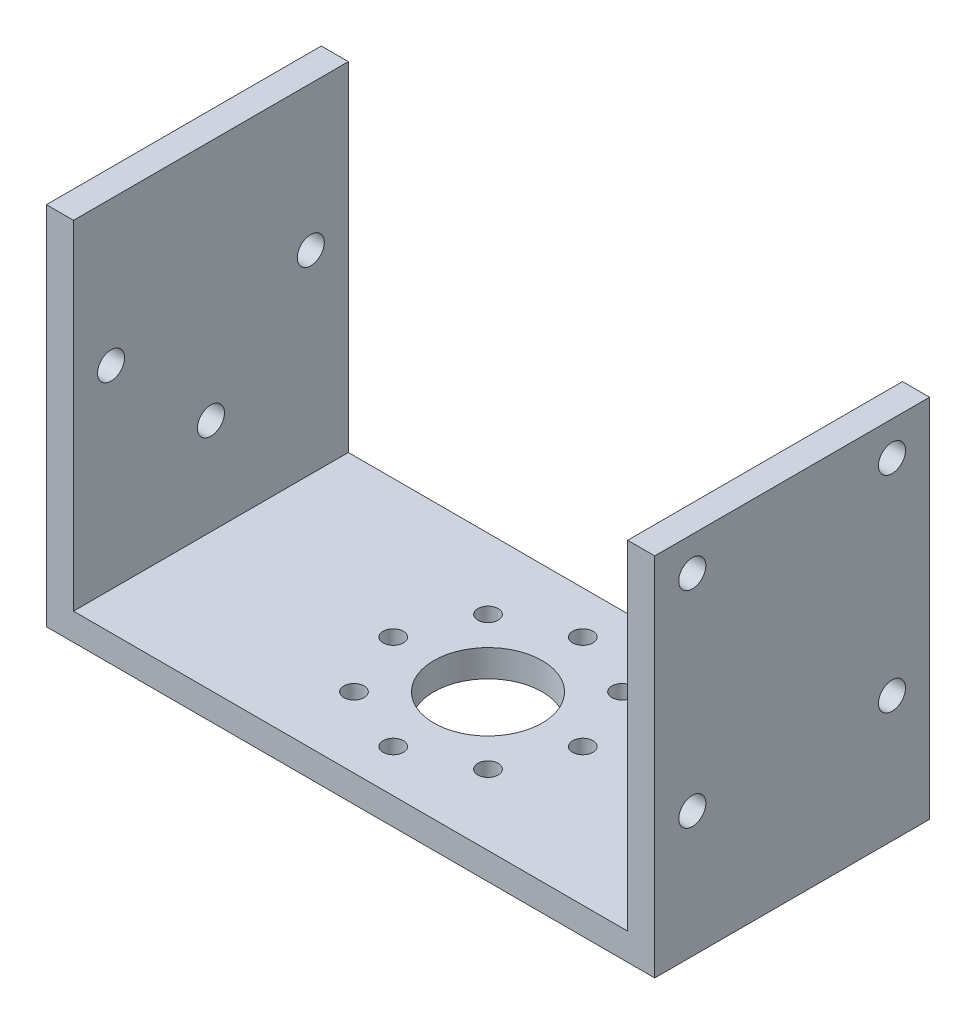
SolidWorks part; units mm, degrees
ref_plane "Front Plane" through (0, 0, 0) normal (0, 0, 1) x (1, 0, 0)
ref_plane "Top Plane" through (0, 0, 0) normal (0, 1, 0) x (1, 0, 0)
ref_plane "Right Plane" through (0, 0, 0) normal (1, 0, 0) x (0, 0, -1)
sketch "Sketch1" plane through (0, 0, 0) normal (0, 1, 0) x (1, 0, 0)
  line L1 (0, 0) -> (44.93, 0)
  line L2 (0, 0) -> (0, 20.3)
  line L3 (0, 20.3) -> (44.93, 20.3)
  line L4 (44.93, 0) -> (44.93, 20.3)
  dimension "D1" = 44.93
  dimension "D2" = 20.3
extrude "YawMount" add sketch "Sketch1" along normal blind 2
sketch "Sketch2" plane through (0, 2, 0) normal (0, 1, 0) x (1, 0, 0)
  line L0 (0, 0) -> (44.93, 0) construction
  line L1 (0, 20.3) -> (2, 20.3)
  line L2 (0, 20.3) -> (0, 0)
  line L3 (0, 0) -> (2, 0)
  line L4 (2, 20.3) -> (2, 0)
  line L6 (44.93, 20.3) -> (42.93, 20.3)
  line L7 (44.93, 20.3) -> (44.93, 0)
  line L8 (44.93, 0) -> (42.93, 0)
  line L9 (42.93, 20.3) -> (42.93, 0)
  dimension "D1" = 2
  dimension "D2" = 2
extrude "BodyConnectors" add sketch "Sketch2" along normal blind 25
sketch "Sketch3" plane through (0, 0, 0) normal (0, -1, 0) x (1, 0, 0)
  line L0 (0, -20.3) -> (0, 0) construction
  line L1 (44.93, -20.3) -> (0, -20.3) construction
  circle A0 centre (22.465, -10.15) radius 4
  point P4 (0, -10.15)
  point P7 (22.465, -20.3)
  dimension "D1" = 8
extrude "Axle-Counterbore" cut sketch "Sketch3" against normal up to surface (2 mm away) up to face at (22.465, 2, -10.15)
sketch "Sketch5" plane through (0, 0, 0) normal (0, -1, 0) x (1, 0, 0)
  line L0 (0, -20.3) -> (0, 0) construction
  line L1 (44.93, -20.3) -> (0, -20.3) construction
  circle A0 centre (15.465, -10.15) radius 0.75
  circle A4 centre (17.5153, -5.2003) radius 0.75
  circle A5 centre (22.465, -3.15) radius 0.75
  circle A6 centre (27.4147, -5.2003) radius 0.75
  circle A7 centre (29.465, -10.15) radius 0.75
  circle A8 centre (27.4147, -15.0997) radius 0.75
  circle A9 centre (22.465, -17.15) radius 0.75
  circle A10 centre (17.5153, -15.0997) radius 0.75
  point P6 (0, -10.15)
  point P24 (22.465, -10.15)
  point P25 (22.465, -20.3)
  dimension "D1" = 1.5
  dimension "D2" = 7
  dimension "D3" = 8
extrude "azel-mountscrews" cut sketch "Sketch5" against normal up to surface (2 mm away) up to face at (22.465, 2, -14.15)
sketch "Sketch6" plane through (2, 0, 0) normal (1, 0, 0) x (0, 0, -1)
  line L0 (0, 27) -> (20.3, 27) construction
  line L3 (0, 2) -> (20.3, 2) construction
  circle A1 centre (10.15, 9.12) radius 1
  circle A2 centre (17.525, 16.33) radius 1
  circle A3 centre (2.775, 16.33) radius 1
  point P5 (10.15, 27)
  dimension "D2" = 2
  dimension "D3" = 14.75
  dimension "D4" = 7.21
  dimension "D5" = 7.375
  dimension "D1" = 7.12
extrude "GearSide-Screws" cut sketch "Sketch6" against normal up to surface (2 mm away) up to face at (0, 13.5, -10.15)
sketch "Sketch7" plane through (42.93, 0, 0) normal (-1, 0, 0) x (0, 0, 1)
  line L0 (-20.3, 2) -> (0, 2) construction
  circle A0 centre (-2.775, 9.3) radius 1
  circle A1 centre (-17.525, 9.3) radius 1
  circle A2 centre (-17.525, 24.5) radius 1
  circle A3 centre (-2.775, 24.5) radius 1
  point P14 (-10.15, 2)
  dimension "D2" = 2
  dimension "D3" = 14.75
  dimension "D1" = 7.3
  dimension "D4" = 7.375
  dimension "D5" = 15.2
extrude "SmoothSide-Screws" cut sketch "Sketch7" against normal up to surface (2 mm away) up to face at (44.93, 13.5, -10.15)
equation "\"srv_w\"= 40.43mm'width of Sain Smart SR319"
equation "\"D1@Sketch1\"=\"srv_w\" + \"mnt_thick\"*2.25"
equation "\"srv_h\"= 40.61mm'height of Sain Smart SR319"
equation "\"srv_d\"= 20.3mm'depth of Sain Smart SR319"
equation "\"D2@Sketch1\"=\"srv_d\""
equation "\"mnt_thick\"= 2mm'thickness of bracket"
equation "\"D1@YawMount\" = \"mnt_thick\""
equation "\"D2@Sketch2\"=\"mnt_thick\""
equation "\"D1@Sketch2\"=\"mnt_thick\""
equation "\"D5@Sketch6\"=\"D3@Sketch6\"/2"
equation "\"D4@Sketch7\"=\"D3@Sketch7\"/2"
equation "\"clearance\"= 5mm'extra space between bracket and roll rotator servo"
equation "\"D1@Sketch6\"=\"clearance\"+2.12mm"
equation "\"D1@Sketch7\"=\"clearance\"+2.3mm"
equation "\"D1@BodyConnectors\"=20+\"clearance\""
